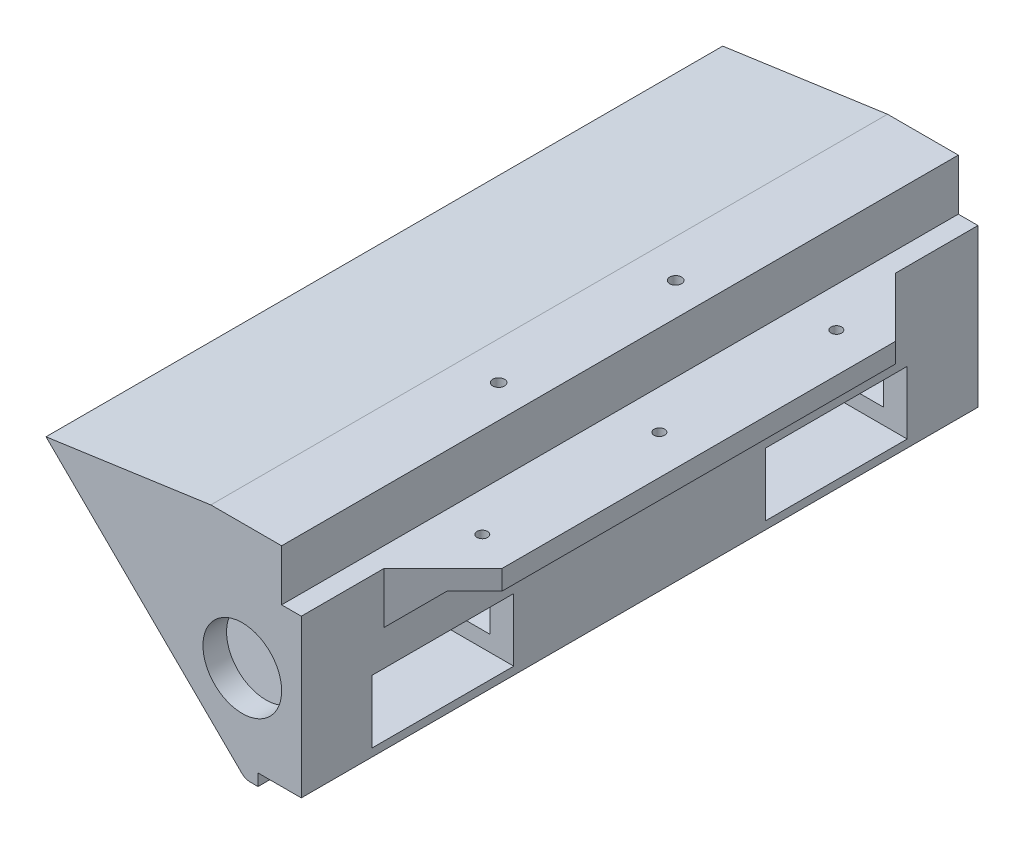
SolidWorks part; units mm, degrees
ref_plane "Front" through (0, 0, 0) normal (0, 0, 1) x (1, 0, 0)
ref_plane "Top" through (0, 0, 0) normal (0, 1, 0) x (1, 0, 0)
ref_plane "Right" through (0, 0, 0) normal (1, 0, 0) x (0, 0, -1)
sketch "草图1" plane through (0, 0, 0) normal (0, 0, 1) x (1, 0, 0)
  line L0 (0, 0) -> (0, 40)
  line L1 (0, 40) -> (-5, 40)
  line L2 (0, 0) -> (-5, 0)
  line L3 (-5, 0) -> (-5, -3)
  line L4 (-5, -3) -> (-13, -3)
  line L5 (-5, 53) -> (-23, 53)
  line L6 (-5, 40) -> (-5, 53)
  line L8 (-15.1213, -2.1213) -> (-64.8886, 47.0507)
  line L10 (-23, 53) -> (-64.8886, 47.0507)
  arc A0 (-15.1213, -2.1213) -> (-13, -3) centre (-13, 0) ccw
extrude "凸台-拉伸1" add sketch "草图1" along normal blind 172
shell "抽壳1" thickness 6
sketch "草图2" plane through (0, 0, 0) normal (1, 0, 0) x (0, 0, -1)
  line L1 (-154, 2) -> (-154, 18)
  line L2 (-154, 18) -> (-118, 18)
  line L3 (-118, 18) -> (-118, 2)
  line L4 (-54, 2) -> (-54, 18)
  line L5 (-54, 18) -> (-18, 18)
  line L6 (-18, 2) -> (-18, 18)
  line L7 (-54, 2) -> (-18, 2)
  line L9 (-154, 2) -> (-118, 2)
extrude "切除-拉伸1" cut sketch "草图2" against normal blind 74
ref_plane "基准面1" through (0, 0, 86) normal (0, 0, -1) x (-1, 0, 0)
sketch "草图3" plane through (0, 0, 86) normal (0, 0, -1) x (-1, 0, 0)
  line L0 (5, 53) -> (5, 40)
  line L1 (5, 40) -> (0, 40)
  line L2 (0, 40) -> (0, 0)
  line L3 (0, 0) -> (5, 0)
  line L4 (5, 0) -> (5, -3)
  line L5 (5, -3) -> (13, -3)
  line L6 (13, -3) -> (16.5794, -0.6807)
  line L7 (64.8886, 47.0507) -> (15.1213, -2.1213) construction
  line L8 (16.5794, -0.6807) -> (64.8886, 47.0507)
  line L9 (64.8886, 47.0507) -> (23, 53)
  line L10 (23, 53) -> (5, 53)
extrude "凸台-拉伸2" add sketch "草图3" along normal mid plane 4 contours L8 L9 L10 L0 L1 L2 L3 L4 L5 L6
sketch "草图4" plane through (0, 0, 172) normal (0, 0, 1) x (1, 0, 0)
  circle A0 centre (-15, 21.0713) radius 10
extrude "切除-拉伸2" cut sketch "草图4" against normal blind 186
sketch "草图5" plane through (0, 53, 0) normal (0, 1, 0) x (1, 0, 0)
  circle A1 centre (-13.3382, -63.5) radius 1.5
  circle A2 centre (-13.3382, -108.5) radius 1.5
extrude "切除-拉伸3" cut sketch "草图5" against normal blind 10
sketch "草图6" plane through (0, 0, 172) normal (0, 0, 1) x (1, 0, 0)
  line L0 (-11, 6) -> (-14.8042, 6)
  line L1 (-52.062, 42.8122) -> (-11.7678, 3) construction
  line L2 (-14.8042, 6) -> (-11.7678, 3)
  line L3 (-11.7678, 3) -> (-11, 3)
  line L4 (-11, 3) -> (-11, 6)
extrude "凸台-拉伸3" add sketch "草图6" against normal blind 172
sketch "草图7" plane through (0, 0, 0) normal (1, 0, 0) x (0, 0, -1)
  line L0 (-154, 18) -> (-154, 2)
  line L1 (-154, 2) -> (-118, 2)
  line L2 (-118, 2) -> (-118, 18)
  line L3 (-118, 18) -> (-154, 18)
  line L4 (-54, 18) -> (-54, 2)
  line L5 (-54, 2) -> (-18, 2)
  line L6 (-18, 2) -> (-18, 18)
  line L7 (-18, 2) -> (-18, 18) construction
  line L8 (-18, 18) -> (-54, 18) construction
  line L9 (-18, 18) -> (-54, 18)
extrude "切除-拉伸4" cut sketch "草图7" against normal blind 172
sketch "草图8" plane through (0, -3, 0) normal (0, -1, 0) x (1, 0, 0)
  line L0 (-5, 172) -> (-11, 172)
  line L1 (-13, 172) -> (-5, 172) construction
  line L2 (-11, 172) -> (-11, 0)
  line L3 (-13, 0) -> (-5, 0) construction
  line L4 (-11, 0) -> (-5, 0)
  line L5 (-5, 0) -> (-5, 172)
extrude "切除-拉伸5" cut sketch "草图8" against normal blind 3
sketch "草图9" plane through (0, 0, 0) normal (1, 0, 0) x (0, 0, -1)
  line L0 (-86, 40) -> (-151, 40)
  line L1 (-172, 40) -> (0, 40) construction
  line L2 (-151, 40) -> (-151, 35)
  line L3 (-151, 35) -> (-86, 35)
  line L4 (-86, -30.8) -> (-86, 30.8) construction
  line L5 (-86, 35) -> (-21, 35)
  line L6 (-21, 35) -> (-21, 40)
  line L7 (-21, 40) -> (-86, 40)
extrude "凸台-拉伸4" add sketch "草图9" along normal blind 15
chamfer "倒角1" distance 15 angle 45 1 edges at (15, 37.5, 151)
chamfer "倒角2" distance 15 angle 45 1 edges at (15, 37.5, 21)
chamfer "倒角3" distance 8 angle 45 1 edges at (0, 35, 86)
sketch "草图10" plane through (0, 0, 0) normal (0, -1, 0) x (1, 0, 0)
  circle A2 centre (-5, 158) radius 1.35
  circle A3 centre (-5, 111) radius 1.35
  circle A4 centre (-5, 61) radius 1.35
  circle A5 centre (-5, 14.0136) radius 1.35
extrude "切除-拉伸6" cut sketch "草图10" against normal blind 15
sketch "草图12" plane through (0, 40, 0) normal (0, 1, 0) x (1, 0, 0)
  line L2 (30.8, -86) -> (-30.8, -86) construction
  circle A1 centre (5, -41) radius 1.35
  circle A2 centre (5, -86) radius 1.35
  circle A3 centre (5, -131) radius 1.35
extrude "切除-拉伸7" cut sketch "草图12" against normal blind 15
sketch "草图14" plane through (0, 0, 84) normal (0, 0, -1) x (-1, 0, 0)
  line L0 (11, 47) -> (6, 34)
  line L1 (6, 34) -> (11, 34)
  line L2 (11, 34) -> (11, 47)
extrude "切除-拉伸8" cut sketch "草图14" along normal blind 78
sketch "草图16" plane through (0, 0, 88) normal (0, 0, 1) x (1, 0, 0)
  line L0 (-11, 47) -> (-11, 34)
  line L1 (-11, 34) -> (-6, 34)
  line L2 (-6, 34) -> (-11, 47)
extrude "切除-拉伸9" cut sketch "草图16" along normal blind 78
